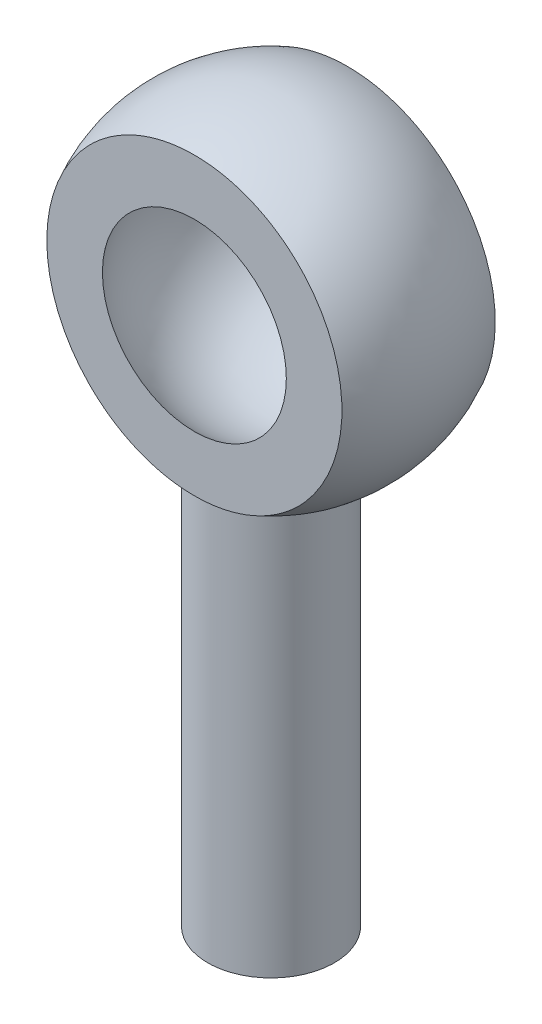
SolidWorks part; units mm, degrees
ref_plane "Front Plane" through (0, 0, 0) normal (0, 0, 1) x (1, 0, 0)
ref_plane "Top Plane" through (0, 0, 0) normal (0, 1, 0) x (1, 0, 0)
ref_plane "Right Plane" through (0, 0, 0) normal (1, 0, 0) x (0, 0, -1)
sketch "Sketch1" plane through (0, 0, 0) normal (0, 1, 0) x (1, 0, 0)
  circle A0 centre (0, 0) radius 4.7625
extrude "Boss-Extrude1" add sketch "Sketch1" along normal blind 42
sketch "Sketch2" plane through (0, 0, 0) normal (0, 0, 1) x (1, 0, 0)
  line L1 (0, 54.5) -> (0, 29.5)
  line L2 (0, -5.2387) -> (0, 5.2387) construction
  line L3 (4.7625, 42) -> (-4.7625, 42) construction
  arc A1 (0, 54.5) -> (0, 29.5) centre (0, 42) ccw
  dimension "D1" = 25
  dimension "D2" = 0
revolve "Revolve4" add sketch "Sketch2" angle 360 about L1
sketch "Sketch4" plane through (0, 0, 0) normal (1, 0, 0) x (0, 0, -1)
  line L1 (-5.7625, 30.4428) -> (-15.7625, 30.4428)
  line L2 (-5.7625, 30.4428) -> (-5.7625, 55.4428)
  line L3 (-5.7625, 55.4428) -> (-15.7625, 55.4428)
  line L4 (-15.7625, 30.4428) -> (-15.7625, 55.4428)
  line L9 (5.76, 30.4428) -> (15.76, 30.4428)
  line L10 (5.76, 30.4428) -> (5.76, 55.4428)
  line L11 (15.76, 30.4428) -> (15.76, 55.4428)
  line L12 (5.76, 55.4428) -> (15.76, 55.4428)
  line L13 (0, 13.75) -> (0, -13.75) construction
  line L15 (-4.7625, 30.4428) -> (4.7625, 30.4428) construction
  dimension "D1" = 0
  dimension "D2" = 10
  dimension "D3" = 10
  dimension "D4" = 5.7625
  dimension "D5" = 5.76
  dimension "D6" = 25
  dimension "D7" = 0
  dimension "D8" = 0
extrude "Cut-Extrude2" cut sketch "Sketch4" against normal through all and the other way through all
sketch "Sketch5" plane through (0, 0, 0) normal (0, 0, 1) x (1, 0, 0)
  line L0 (0, 54.5) -> (0, 29.5) construction
  line L1 (0, 51) -> (0, 33)
  arc A0 (0, 51) -> (0, 33) centre (0, 42) ccw
  dimension "D1" = 18
revolve "Cut-Revolve1" cut sketch "Sketch5" angle 360 about L1
